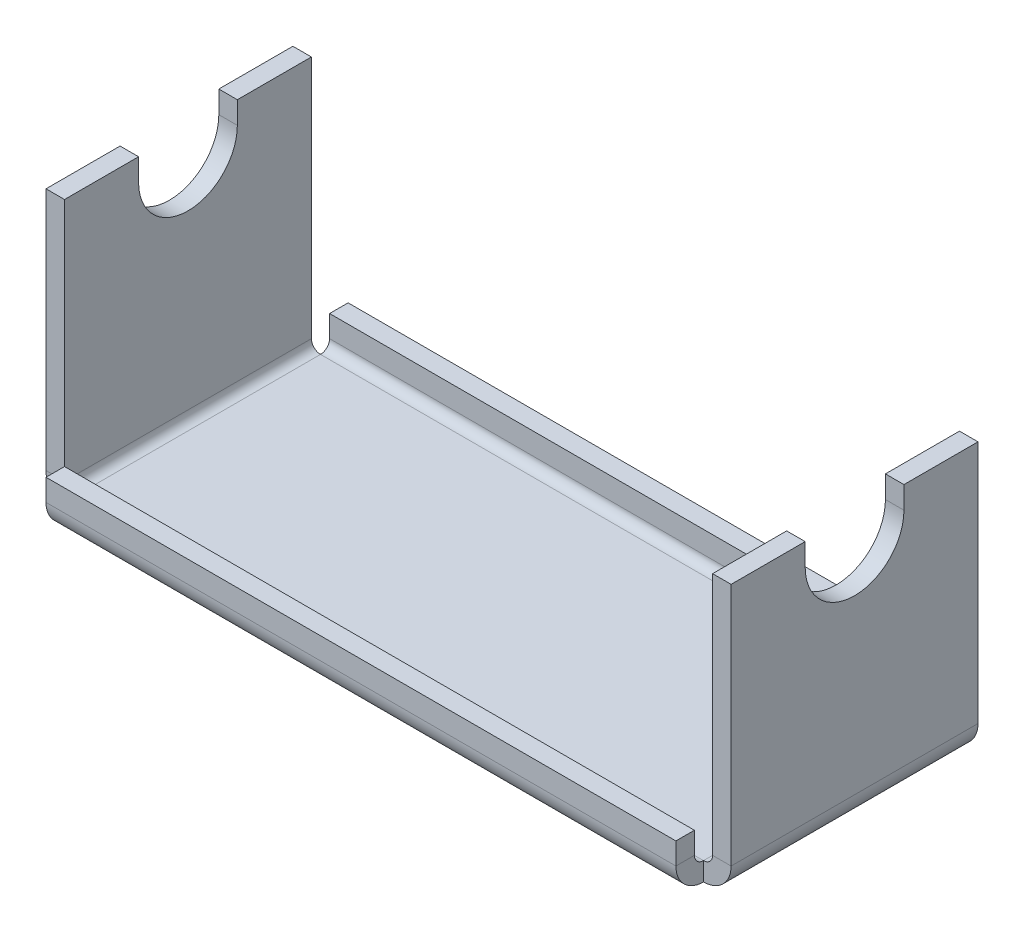
SolidWorks part; units mm, degrees
note: The reader was unsure of these and kept them because the rebuilt part matched: flange length of "Brida de arista1", "Brida de arista2".
ref_plane "Alzado" through (0, 0, 0) normal (0, 0, 1) x (1, 0, 0)
ref_plane "Planta" through (0, 0, 0) normal (0, 1, 0) x (1, 0, 0)
ref_plane "Vista lateral" through (0, 0, 0) normal (1, 0, 0) x (0, 0, -1)
sketch "Croquis3" plane through (0, 0, 0) normal (0, 1, 0) x (1, 0, 0)
  line L1 (-27.75, -10) -> (27.75, -10)
  line L2 (-27.75, -10) -> (-27.75, 10)
  line L3 (-27.75, 10) -> (27.75, 10)
  line L4 (27.75, -10) -> (27.75, 10)
  line L5 (-27.75, -10) -> (27.75, 10) construction
  line L6 (-27.75, 10) -> (27.75, -10) construction
  point P0 (0, 0)
  dimension "D1" = 55.5
  dimension "D2" = 20
base flange "Brida base1" sketch "Croquis3" thickness 1.5 reverse thickness direction no parameters "D1"=0.7366
edge flange "Brida de arista1" sketch "Croquis12" flange profiles "Croquis12", "Croquis13" flange angle 90 flange length 22 flange position material inside bend radius 0.7366 thickness 1.5 relief rectangular parameters "D6"=10, "D8"=0.5
sketch "Croquis12" plane through (-27.75, 0, 0) normal (-1, 0, 0) x (0, 0, 1)
  line L2 (-10, 0) -> (-10, 20.5)
  line L3 (-10, 20.5) -> (10, 20.5)
  line L4 (10, 20.5) -> (10, 0)
  line L7 (-10, 0) -> (10, 0) construction
  line L8 (-10, 0) -> (10, 0)
sketch "Croquis13" plane through (27.75, 0, 0) normal (1, 0, 0) x (0, 0, -1)
  line L0 (-10, 0) -> (10, 0) construction
  line L1 (-10, 0) -> (10, 0)
  line L2 (-10, 0) -> (-10, 20.5)
  line L3 (-10, 20.5) -> (10, 20.5)
  line L4 (10, 20.5) -> (10, 0)
bend "Pliegue de arista1" bend radius 0.7366 bend angle 90 parameters "D5"=1
bend "Pliegue de arista2" bend radius 0.7366 bend angle 90 parameters "D5"=2
edge flange "Brida de arista2" sketch "Croquis18" flange profiles "Croquis18", "Croquis19" flange angle 90 flange length 4 flange position bend outside bend radius 0.7366 thickness 1.5 relief rectangular parameters "D6"=10, "D8"=0.5
sketch "Croquis18" plane through (0, 0, 10) normal (0, 0, 1) x (1, 0, 0)
  line L0 (-25.5134, 0) -> (25.5134, 0) construction
  line L1 (-25.5134, 0) -> (25.5134, 0)
  line L2 (-25.5134, 0) -> (-25.5134, 2.5)
  line L3 (-25.5134, 2.5) -> (25.5134, 2.5)
  line L4 (25.5134, 2.5) -> (25.5134, 0)
sketch "Croquis19" plane through (0, 0, -10) normal (0, 0, -1) x (-1, 0, 0)
  line L0 (-25.5134, 0) -> (25.5134, 0) construction
  line L1 (-25.5134, 0) -> (25.5134, 0)
  line L2 (-25.5134, 0) -> (-25.5134, 2.5)
  line L3 (-25.5134, 2.5) -> (25.5134, 2.5)
  line L4 (25.5134, 2.5) -> (25.5134, 0)
bend "Pliegue de arista3" bend radius 0.7366 bend angle 90 parameters "D5"=3
bend "Pliegue de arista4" bend radius 0.7366 bend angle 90 parameters "D5"=4
sketch "Croquis20" plane through (27.75, 0, 0) normal (1, 0, 0) x (0, 0, -1)
  line L0 (0, 20.5) -> (0, 18.7) construction
  line L1 (10, 20.5) -> (-10, 20.5) construction
  line L2 (4, 18.7) -> (4, 22.7)
  line L3 (4, 22.7) -> (-4, 22.7)
  line L4 (-4, 22.7) -> (-4, 18.7)
  arc A0 (-4, 18.7) -> (4, 18.7) centre (0, 18.7) ccw
  dimension "D2" = 8
  dimension "D1" = 1.8
extrude "Cortar-Extruir1" cut sketch "Croquis20" against normal up to surface (55.5 mm away) normal cut yes up to face at (-27.75, 10.6183, 0)
sketch "Líneas de pliegue1" [suppressed] plane through (0, 0, 0) normal (0, 1, 0) x (1, 0, 0)
sketch "Cuadro delimitador1" [suppressed] plane through (0, 0, 0) normal (0, 1, 0) x (1, 0, 0)
sheet metal parameters "Chapa metálica3" thickness 1.5 parameters "D1"=0.7366
flat pattern "Chapa desplegada3" [suppressed]
sketch "Líneas de pliegue2" plane through (0, 0, 0) normal (0, 1, 0) x (1, 0, 0)
sketch3d "Cuadro delimitador2" [suppressed]
  line L0 (-27.75, 10, 0) -> (27.75, 10, 0) construction
  line L1 (-27.75, -10, 0) -> (27.75, -10, 0) construction
  line L2 (-27.75, 10, 0) -> (-27.75, -10, 0) construction
  line L3 (27.75, 10, 0) -> (27.75, -10, 0) construction
sheet metal parameters "Chapa metálica4" thickness 1.5 parameters "D1"=0.7366
flat pattern "Chapa desplegada3"
sketch "Líneas de pliegue2" plane through (0, 0, 0) normal (0, 1, 0) x (1, 0, 0)
  line L0 (26.681, -10) -> (26.681, 10) construction
  line L1 (-26.681, 10) -> (-26.681, -10) construction
  line L2 (26.681, -10) -> (26.681, 10) construction
  line L3 (-26.681, 10) -> (-26.681, -10) construction
sketch3d "Cuadro delimitador2" [suppressed]
  line L0 (47.6119, 10, 0) -> (-47.6119, 10, 0) construction
  line L1 (47.6119, -10, 0) -> (-47.6119, -10, 0) construction
  line L2 (47.6119, 10, 0) -> (47.6119, -10, 0) construction
  line L3 (-47.6119, 10, 0) -> (-47.6119, -10, 0) construction
bend of the flat pattern "Aplanar-<Pliegue de arista1>1"
bend of the flat pattern "Aplanar-<Pliegue de arista2>1"
sheet metal parameters "Chapa metálica5" thickness 1.5 parameters "D1"=0.7366
flat pattern "Chapa desplegada3"
sketch "Líneas de pliegue2" plane through (0, 0, 0) normal (0, 1, 0) x (1, 0, 0)
  line L0 (26.681, -10) -> (26.681, 10) construction
  line L1 (-26.681, 10) -> (-26.681, -10) construction
  line L2 (26.681, -10) -> (26.681, 10) construction
  line L3 (-26.681, 10) -> (-26.681, -10) construction
  line L4 (25.5134, 11.1676) -> (-25.5134, 11.1676) construction
  line L5 (-25.5134, -11.1676) -> (25.5134, -11.1676) construction
  line L6 (25.5134, 11.1676) -> (-25.5134, 11.1676) construction
  line L7 (-25.5134, -11.1676) -> (25.5134, -11.1676) construction
sketch3d "Cuadro delimitador2" [suppressed]
  line L0 (47.6119, 14.0985, 0) -> (-47.6119, 14.0985, 0) construction
  line L1 (47.6119, -14.0985, 0) -> (-47.6119, -14.0985, 0) construction
  line L2 (47.6119, 14.0985, 0) -> (47.6119, -14.0985, 0) construction
  line L3 (-47.6119, 14.0985, 0) -> (-47.6119, -14.0985, 0) construction
bend of the flat pattern "Aplanar-<Pliegue de arista1>1"
bend of the flat pattern "Aplanar-<Pliegue de arista2>1"
bend of the flat pattern "Aplanar-<Pliegue de arista3>1"
bend of the flat pattern "Aplanar-<Pliegue de arista4>1"
sheet metal parameters "Chapa metálica6" thickness 1.5 parameters "D1"=0.7366
flat pattern "Chapa desplegada3"
sketch "Líneas de pliegue2" plane through (0, 0, 0) normal (0, 1, 0) x (1, 0, 0)
  line L0 (26.681, -10) -> (26.681, 10) construction
  line L1 (-26.681, 10) -> (-26.681, -10) construction
  line L2 (26.681, -10) -> (26.681, 10) construction
  line L3 (-26.681, 10) -> (-26.681, -10) construction
  line L4 (25.5134, 11.1676) -> (-25.5134, 11.1676) construction
  line L5 (-25.5134, -11.1676) -> (25.5134, -11.1676) construction
  line L6 (25.5134, 11.1676) -> (-25.5134, 11.1676) construction
  line L7 (-25.5134, -11.1676) -> (25.5134, -11.1676) construction
sketch3d "Cuadro delimitador2" [suppressed]
  line L0 (47.6119, 14.0985, 0) -> (-47.6119, 14.0985, 0) construction
  line L1 (47.6119, -14.0985, 0) -> (-47.6119, -14.0985, 0) construction
  line L2 (47.6119, 14.0985, 0) -> (47.6119, -14.0985, 0) construction
  line L3 (-47.6119, 14.0985, 0) -> (-47.6119, -14.0985, 0) construction
bend of the flat pattern "Aplanar-<Pliegue de arista1>1"
bend of the flat pattern "Aplanar-<Pliegue de arista2>1"
bend of the flat pattern "Aplanar-<Pliegue de arista3>1"
bend of the flat pattern "Aplanar-<Pliegue de arista4>1"
